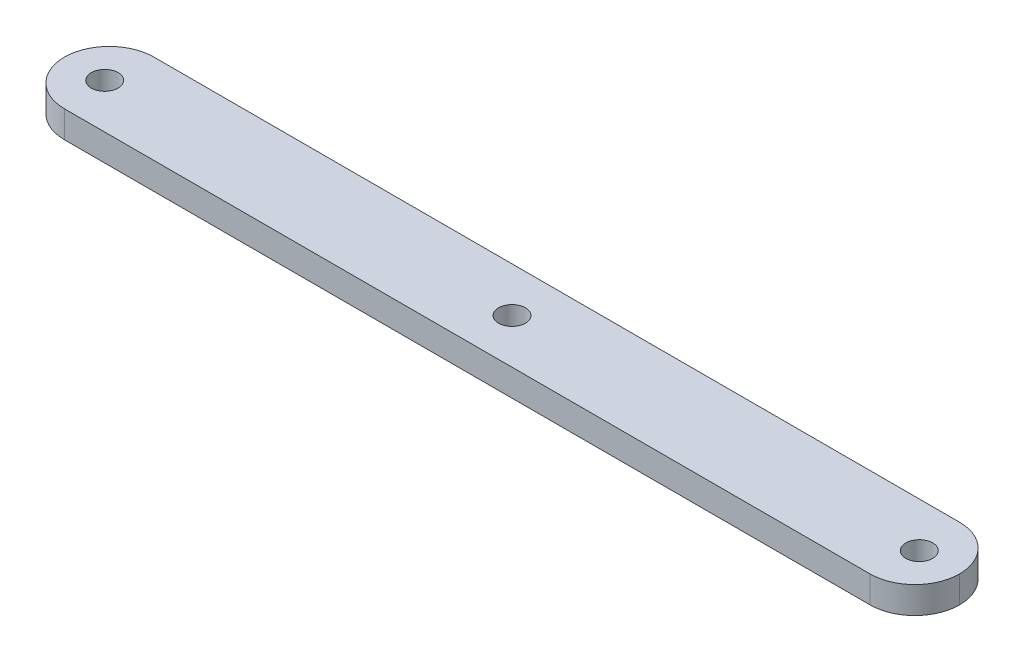
SolidWorks part; units mm, degrees
ref_plane "Front Plane" through (0, 0, 0) normal (0, 0, 1) x (1, 0, 0)
ref_plane "Top Plane" through (0, 0, 0) normal (0, 1, 0) x (1, 0, 0)
ref_plane "Right Plane" through (0, 0, 0) normal (1, 0, 0) x (0, 0, -1)
sketch "Sketch2" plane through (0, 0, 0) normal (0, 1, 0) x (1, 0, 0)
  line L1 (0, 0) -> (200, 0)
  line L2 (0, 0) -> (0, 20)
  line L3 (0, 20) -> (200, 20)
  line L4 (200, 0) -> (200, 20)
  dimension "D1" = 200
  dimension "D2" = 20
extrude "Boss-Extrude1" add sketch "Sketch2" along normal blind 6
sketch "Sketch3" plane through (0, 6, 0) normal (0, 1, 0) x (1, 0, 0)
  line L0 (200, 20) -> (0, 20) construction
  line L1 (0, 20) -> (0, 0) construction
  circle A0 centre (9, 10) radius 3
  dimension "D1" = 10
  dimension "D2" = 9
  dimension "D3" = 6
extrude "Cut-Extrude1" cut sketch "Sketch3" against normal through all
sketch "Sketch4" plane through (0, 6, 0) normal (0, 1, 0) x (1, 0, 0)
  line L0 (200, 20) -> (0, 20) construction
  line L1 (200, 0) -> (200, 20) construction
  circle A0 centre (191, 10) radius 3
  dimension "D1" = 10
  dimension "D3" = 6
  dimension "D2" = 9
extrude "Cut-Extrude2" cut sketch "Sketch4" against normal through all
fillet "Fillet1" radius 10 2 edges at (0, 3, -20) (0, 3, 0)
fillet "Fillet2" radius 10 2 edges at (200, 3, -20) (200, 3, 0)
sketch "Sketch6" plane through (0, 6, 0) normal (0, 1, 0) x (1, 0, 0)
  line L2 (190, 20) -> (10, 20) construction
  line L3 (10, 0) -> (190, 0) construction
  circle A0 centre (100, 10) radius 3
  dimension "D1" = 6
  dimension "D3" = 20
  dimension "D4" = 10
extrude "Cut-Extrude3" cut sketch "Sketch6" against normal through all
sketch "Sketch7" plane through (0, 6, 0) normal (0, 1, 0) x (1, 0, 0)
  line L0 (190, 20) -> (10, 20) construction
  line L1 (19, 15) -> (90, 15)
  line L2 (19, 15) -> (19, 5)
  line L3 (19, 5) -> (90, 5)
  line L4 (90, 15) -> (90, 5)
  line L5 (10, 0) -> (190, 0) construction
  line L7 (110, 15) -> (181, 15)
  line L8 (110, 15) -> (110, 5)
  line L9 (110, 5) -> (181, 5)
  line L10 (181, 15) -> (181, 5)
  circle A0 centre (9, 10) radius 3 construction
  circle A1 centre (100, 10) radius 3 construction
  circle A2 centre (191, 10) radius 3 construction
  dimension "D5" = 10
  dimension "D1" = 5
  dimension "D2" = 5
  dimension "D3" = 10
  dimension "D4" = 10
  dimension "D6" = 10
extrude "Cut-Extrude4" [suppressed] cut sketch "Sketch7" against normal blind 10
